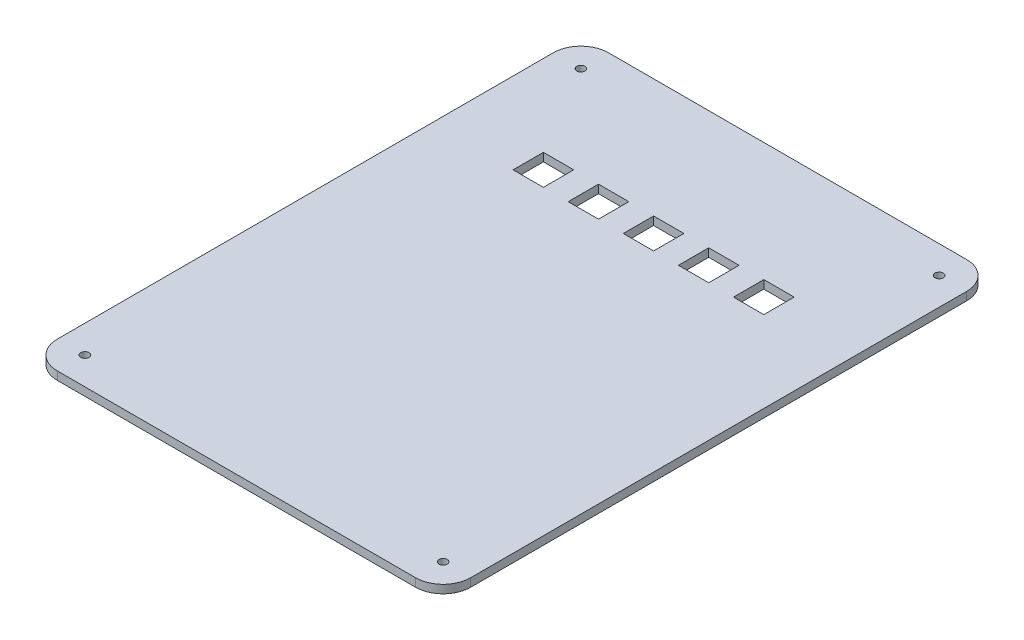
SolidWorks part; units mm, degrees
ref_plane "Спереди" through (0, 0, 0) normal (0, 0, 1) x (1, 0, 0)
ref_plane "Сверху" through (0, 0, 0) normal (0, 1, 0) x (1, 0, 0)
ref_plane "Справа" through (0, 0, 0) normal (1, 0, 0) x (0, 0, -1)
sketch "Эскиз1" plane through (0, 0, 0) normal (0, 1, 0) x (1, 0, 0)
  line L1 (75, -100) -> (-75, -100)
  line L2 (75, -100) -> (75, 100)
  line L3 (75, 100) -> (-75, 100)
  line L4 (-75, -100) -> (-75, 100)
  line L5 (75, -100) -> (-75, 100) construction
  line L6 (75, 100) -> (-75, -100) construction
  point P0 (0, 0)
  dimension "D1" = 200
  dimension "D2" = 150
extrude "Бобышка-Вытянуть1" add sketch "Эскиз1" along normal mid plane 3
fillet "Скругление1" radius 10 4 edges at (-75, 0, -100) (75, 0, -100) (75, 0, 100) (-75, 0, 100)
sketch "Эскиз2" plane through (0, 1.5, 0) normal (0, 1, 0) x (1, 0, 0)
  line L0 (0, 0) -> (0, -33.246) construction
  line L1 (0, 0) -> (-47.6996, 0) construction
  circle A0 centre (-65, 90) radius 1.5
  circle A1 centre (-65, -90) radius 1.5
  circle A2 centre (65, -90) radius 1.5
  circle A3 centre (65, 90) radius 1.5
extrude "Вырез-Вытянуть1" cut sketch "Эскиз2" against normal up to surface (3 mm away) up to face at (0, -1.5, 0)
sketch "Эскиз3" plane through (0, 1.5, 0) normal (0, 1, 0) x (1, 0, 0)
  line L0 (-34.5, 56.8905) -> (-34.5, 44.834)
  line L1 (45.5, 45.8905) -> (34.5, 45.8905)
  line L2 (45.5, 45.8905) -> (45.5, 56.8905)
  line L3 (45.5, 56.8905) -> (34.5, 56.8905)
  line L4 (-45.5, 45.8905) -> (-45.5, 56.8905)
  line L5 (45.5, 45.8905) -> (34.5, 47.2202) construction
  line L6 (45.5, 56.8905) -> (34.5, 55.5609) construction
  line L7 (-25.5, 56.8905) -> (-25.5, 45.8905)
  line L8 (34.5, 56.8905) -> (34.5, 45.8905)
  line L9 (25.5, 56.8905) -> (25.5, 45.8905)
  line L10 (14.5, 56.8905) -> (14.5, 45.8905)
  line L11 (5.5, 56.8905) -> (5.5, 45.8905)
  line L12 (-5.5, 56.8905) -> (-5.5, 45.8905)
  line L13 (-14.5, 56.8905) -> (-14.5, 45.8905)
  line L14 (-34.5, 56.8905) -> (-45.5, 56.8905)
  line L15 (-34.5, 55.5609) -> (-45.5, 56.8905) construction
  line L16 (-34.5, 47.2202) -> (-45.5, 45.8905) construction
  line L17 (-34.5, 45.8905) -> (-45.5, 45.8905)
  line L18 (-14.5, 56.8905) -> (-25.5, 56.8905)
  line L19 (-14.5, 53.1433) -> (-25.5, 54.473) construction
  line L20 (-14.5, 49.6378) -> (-25.5, 48.3081) construction
  line L21 (-14.5, 45.8905) -> (-25.5, 45.8905)
  line L22 (5.5, 56.8905) -> (-5.5, 56.8905)
  line L23 (5.5, 52.0554) -> (-5.5, 50.7257) construction
  line L24 (5.5, 50.7257) -> (-5.5, 52.0554) construction
  line L25 (5.5, 45.8905) -> (-5.5, 45.8905)
  line L26 (25.5, 56.8905) -> (14.5, 56.8905)
  line L27 (25.5, 54.473) -> (14.5, 53.1433) construction
  line L28 (25.5, 48.3081) -> (14.5, 49.6378) construction
  line L29 (25.5, 45.8905) -> (14.5, 45.8905)
  point P0 (0, 51.3905)
  point P14 (25.5, 51.3905)
  dimension "D1" = 11
  dimension "D2" = 91
  dimension "D3" = 11
  dimension "D4" = 9
  dimension "D5" = 11
  dimension "D6" = 9
  dimension "D7" = 11
  dimension "D8" = 9
  dimension "D9" = 11
  dimension "D10" = 9
extrude "Вырез-Вытянуть2" cut sketch "Эскиз3" against normal up to surface (3 mm away) contours L17 L0 L14 L4 | L21 L13 L18 L7 | L25 L11 L22 L12 | L29 L9 L26 L10 | L3 L8 L1 L2 region at (-40, 1.5, -51.3905) region at (40, 1.5, -51.3905) region at (-20, 1.5, -51.3905) region at (20, 1.5, -51.3905) region at (0, 1.5, -51.3905) up to face at (65, -1.5, -88.5)
